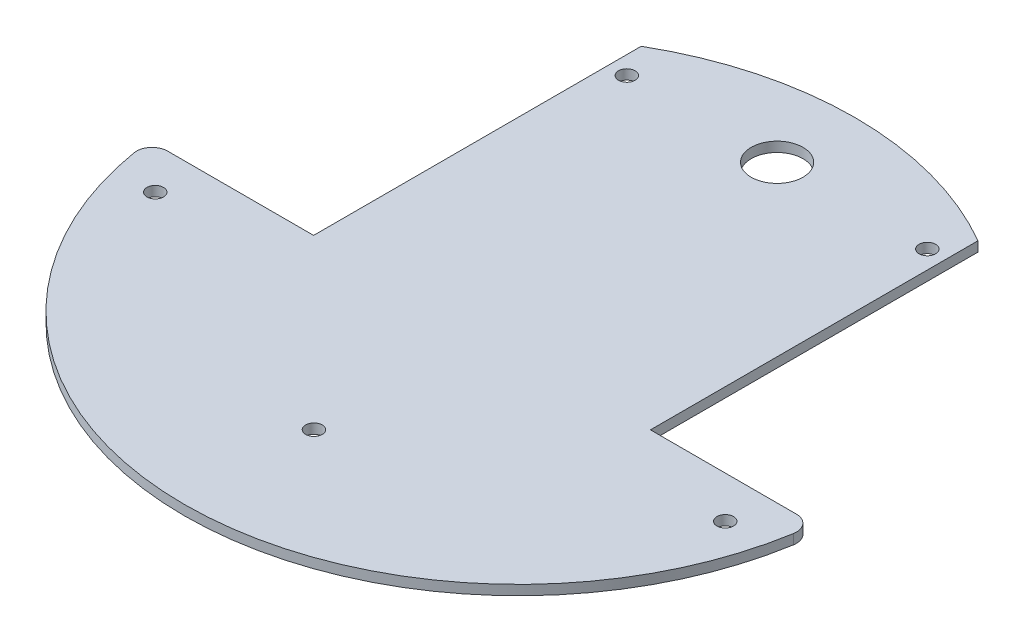
SolidWorks part; units mm, degrees
material "ABS"
ref_plane "Front Plane" through (0, 0, 0) normal (0, 0, 1) x (1, 0, 0)
ref_plane "Top Plane" through (0, 0, 0) normal (0, 1, 0) x (1, 0, 0)
ref_plane "Right Plane" through (0, 0, 0) normal (1, 0, 0) x (0, 0, -1)
sketch "Sketch1" plane through (0, 0, 0) normal (0, 1, 0) x (1, 0, 0)
  line L1 (-18, -10) -> (18, -10)
  line L2 (-18, -10) -> (-18, 10)
  line L3 (-18, 10) -> (18, 10)
  line L4 (18, -10) -> (18, 10)
  line L5 (-18, -10) -> (18, 10) construction
  line L6 (-18, 10) -> (18, -10) construction
  point P0 (0, 0)
  dimension "D1" = 36
  dimension "D2" = 20
extrude "Boss-Extrude1" add sketch "Sketch1" along normal blind 1.9
sketch "Sketch2" plane through (0, 0, 0) normal (0, -1, 0) x (1, 0, 0)
  line L0 (0, -10) -> (0, 10) construction
  line L1 (18, -10) -> (-18, -10) construction
  line L2 (-18, 10) -> (18, 10) construction
sketch "Sketch3" plane through (0, 0, 0) normal (0, -1, 0) x (1, 0, 0)
  line L0 (0, 0) -> (0, 52.1486) construction
  line L1 (37.5, -26.8695) -> (-37.5, -26.8695) construction
  line L2 (37.5, -26.8695) -> (32.5, -26.8695)
  line L3 (0, 0) -> (0, -36.2287) construction
  line L4 (-37.5, -26.8695) -> (-32.5, -26.8695)
  line L5 (32.5, -26.8695) -> (32.5, 33.1305)
  line L6 (-32.5, -26.8695) -> (-32.5, 33.1305)
  line L7 (32.5, 33.1305) -> (60.6723, 33.1305)
  line L9 (-32.5, 33.1305) -> (-60.6723, 33.1305)
  arc A0 (37.5, -26.8695) -> (-37.5, -26.8695) centre (0, 26.0743) cw
  arc A1 (-34.7347, -37.0735) -> (34.2438, -37.3411) centre (0, 26.0743) ccw construction
  arc A2 (68.1909, 19.5743) -> (-68.1909, 19.5743) centre (0, 26.0743) ccw construction
  arc A3 (63.6319, 36.621) -> (-63.6319, 36.621) centre (0, 26.0743) ccw
  circle A4 centre (0, 26.0743) radius 72.5 construction
  arc A5 (-60.6723, 33.1305) -> (-63.6319, 36.621) centre (-60.6723, 36.1305) cw
  arc A6 (60.6723, 33.1305) -> (63.6319, 36.621) centre (60.6723, 36.1305) ccw
  point P7 (0, 26.0743)
  point P20 (-64.1129, 33.1305)
  point P26 (64.1129, 33.1305)
  dimension "D1" = 4
  dimension "D3" = 5
  dimension "D4" = 60
  dimension "D5" = 3
  dimension "D6" = 7.0562
  dimension "D2" = 65
extrude "Boss-Extrude2" add sketch "Sketch3" against normal blind 1.9
sketch "Sketch4" plane through (0, 1.9, 0) normal (0, 1, 0) x (1, 0, 0)
  line L0 (-32.5, 26.8695) -> (-32.5, 34.1947)
  line L1 (-32.5, 34.1947) -> (-40.4421, 34.1947)
  line L2 (-40.4421, 34.1947) -> (-37.5, 26.8695)
  line L3 (-37.5, 26.8695) -> (-32.5, 26.8695)
  line L4 (0, 0) -> (0, 49.3906) construction
  line L5 (37.5, 26.8695) -> (32.5, 26.8695)
  line L6 (40.4421, 34.1947) -> (37.5, 26.8695)
  line L7 (32.5, 34.1947) -> (40.4421, 34.1947)
  line L8 (32.5, 26.8695) -> (32.5, 34.1947)
  arc A0 (37.5, 26.8695) -> (-37.5, 26.8695) centre (0, -26.0743) ccw construction
extrude "Cut-Extrude1" cut sketch "Sketch4" against normal blind 10
sketch "Sketch5" plane through (0, 1.9, 0) normal (0, 1, 0) x (1, 0, 0)
  line L0 (0, 0) -> (0, 38.8048) construction
  circle A0 centre (0, 23.8048) radius 5
  arc A1 (32.5, 30.0777) -> (-32.5, 30.0777) centre (0, -26.0743) ccw construction
  dimension "D1" = 10
  dimension "D2" = 15
extrude "Cut-Extrude2" cut sketch "Sketch5" against normal up to surface (1.9 mm away) up to face at (0, 0, 23.683)
sketch "Sketch6" plane through (0, 1.9, 0) normal (0, 1, 0) x (1, 0, 0)
  line L0 (0, 38.8048) -> (0, -90.5743) construction
  line L1 (-55, -41.1952) -> (55, -41.1952) construction
  line L2 (-29, 23.8048) -> (29, 23.8048) construction
  arc A0 (32.5, 30.0777) -> (-32.5, 30.0777) centre (0, -26.0743) ccw construction
  arc A1 (-63.6319, -36.621) -> (63.6319, -36.621) centre (0, -26.0743) ccw construction
  circle A2 centre (0, -65.5743) radius 1.6
  circle A3 centre (-55, -41.1952) radius 1.6
  circle A4 centre (55, -41.1952) radius 1.6
  circle A5 centre (-29, 23.8048) radius 1.6
  circle A6 centre (29, 23.8048) radius 1.6
  dimension "D1" = 25
  dimension "D2" = 3.2
  dimension "D3" = 55
  dimension "D5" = 58
  dimension "D4" = 80
  dimension "D6" = 65
extrude "Cut-Extrude3" cut sketch "Sketch6" against normal up to surface (1.9 mm away) up to face at (0, 0, -28.8048)
